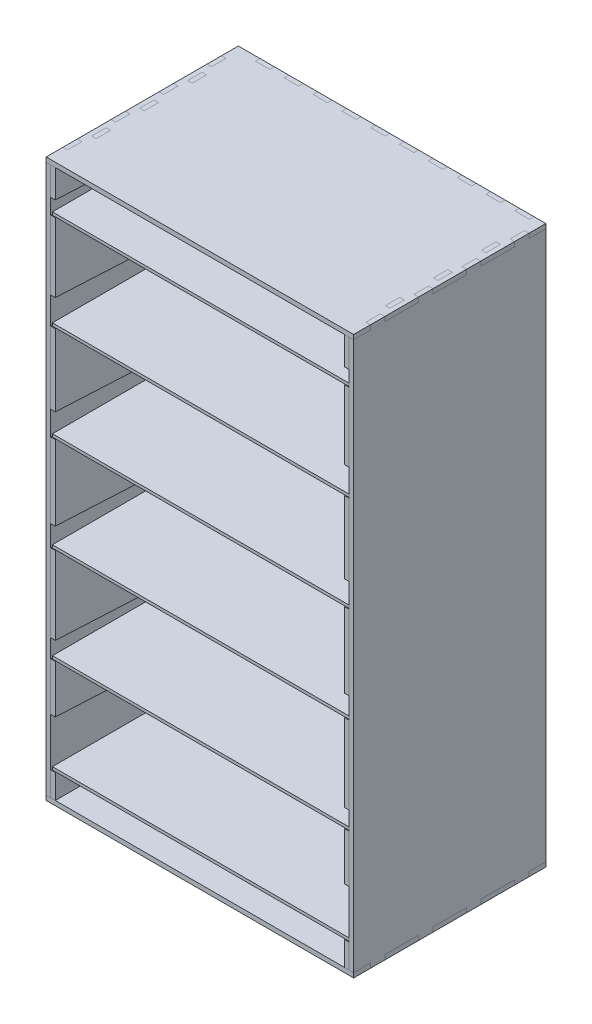
SolidWorks part; units mm, degrees
ref_plane "Front Plane" through (0, 0, 0) normal (0, 0, 1) x (1, 0, 0)
ref_plane "Top Plane" through (0, 0, 0) normal (0, 1, 0) x (1, 0, 0)
ref_plane "Right Plane" through (0, 0, 0) normal (1, 0, 0) x (0, 0, -1)
sketch "Sketch1" plane through (0, 0, 0) normal (0, 0, 1) x (1, 0, 0)
  line L0 (-160, -260) -> (160, -260)
  line L1 (160, -290) -> (-160, -290)
  line L2 (160, -290) -> (160, 290)
  line L3 (160, 290) -> (-160, 290)
  line L4 (-160, -290) -> (-160, 290)
  line L5 (160, -290) -> (-160, 290) construction
  line L6 (160, 290) -> (-160, -290) construction
  line L7 (-160, -160) -> (160, -160)
  line L8 (-160, -60) -> (160, -60)
  line L9 (-160, 40) -> (160, 40)
  line L10 (-160, 140) -> (160, 140)
  line L11 (-160, 240) -> (160, 240)
  point P0 (0, 0)
  dimension "D1" = 320
  dimension "D2" = 580
  dimension "D4" = 30
  dimension "D5" = 100
  dimension "D3" = 6
sketch "Sketch2" plane through (0, 0, 0) normal (0, 0, 1) x (1, 0, 0)
  line L0 (160, -290) -> (160, 290) construction
  line L1 (-160, 290) -> (160, 290)
  line L2 (-160, 290) -> (-160, 285.25)
  line L3 (-160, 285.25) -> (160, 285.25)
  line L4 (160, 290) -> (160, 285.25)
  line L6 (-160, -290) -> (160, -290)
  line L7 (-160, -290) -> (-160, -285.25)
  line L8 (-160, -285.25) -> (160, -285.25)
  line L9 (160, -290) -> (160, -285.25)
  dimension "D1" = 4.75
sketch "Sketch3" plane through (0, 0, 0) normal (0, 1, 0) x (1, 0, 0)
  line L0 (160, 0) -> (-160, 0) construction
  line L1 (-160, 0) -> (160, 0)
  line L2 (-160, 0) -> (-160, -200)
  line L3 (-160, -200) -> (160, -200)
  line L4 (160, 0) -> (160, -200)
  line L5 (160, 0) -> (-160, 0) construction
  line L6 (-155.25, 0) -> (-155.25, -200) construction
  line L7 (-150.5, 0) -> (-150.5, -200) construction
  line L8 (-155.25, -67.5) -> (-160, -67.5)
  line L9 (-155.25, -17.5) -> (-160, -17.5)
  line L10 (-155.25, -17.5) -> (-155.25, -32.5)
  line L11 (-155.25, -32.5) -> (-160, -32.5)
  line L12 (-160, -17.5) -> (-160, -32.5)
  line L13 (-155.25, -17.5) -> (-160, -32.5) construction
  line L14 (-155.25, -32.5) -> (-160, -17.5) construction
  line L15 (-150.5, -57.5) -> (-155.25, -57.5)
  line L16 (-150.5, -57.5) -> (-150.5, -42.5)
  line L17 (-150.5, -42.5) -> (-155.25, -42.5)
  line L18 (-155.25, -57.5) -> (-155.25, -42.5)
  line L19 (-150.5, -57.5) -> (-155.25, -42.5) construction
  line L20 (-150.5, -42.5) -> (-155.25, -57.5) construction
  line L21 (-155.25, -67.5) -> (-155.25, -82.5)
  line L22 (-155.25, -82.5) -> (-160, -82.5)
  line L23 (-160, -67.5) -> (-160, -82.5)
  line L24 (-150.5, -107.5) -> (-155.25, -107.5)
  line L25 (-150.5, -107.5) -> (-150.5, -92.5)
  line L26 (-150.5, -92.5) -> (-155.25, -92.5)
  line L27 (-155.25, -107.5) -> (-155.25, -92.5)
  line L28 (-155.25, -67.5) -> (-160, -82.5) construction
  line L29 (-155.25, -82.5) -> (-160, -67.5) construction
  line L30 (-150.5, -107.5) -> (-155.25, -92.5) construction
  line L31 (-150.5, -92.5) -> (-155.25, -107.5) construction
  line L32 (-155.25, -117.5) -> (-160, -117.5)
  line L33 (-155.25, -117.5) -> (-155.25, -132.5)
  line L34 (-155.25, -132.5) -> (-160, -132.5)
  line L35 (-160, -117.5) -> (-160, -132.5)
  line L36 (-150.5, -157.5) -> (-155.25, -157.5)
  line L37 (-150.5, -157.5) -> (-150.5, -142.5)
  line L38 (-150.5, -142.5) -> (-155.25, -142.5)
  line L39 (-155.25, -157.5) -> (-155.25, -142.5)
  line L40 (-155.25, -117.5) -> (-160, -132.5) construction
  line L41 (-155.25, -132.5) -> (-160, -117.5) construction
  line L42 (-150.5, -157.5) -> (-155.25, -142.5) construction
  line L43 (-150.5, -142.5) -> (-155.25, -157.5) construction
  line L44 (-155.25, -167.5) -> (-160, -167.5)
  line L45 (-155.25, -167.5) -> (-155.25, -182.5)
  line L46 (-155.25, -182.5) -> (-160, -182.5)
  line L47 (-160, -167.5) -> (-160, -182.5)
  line L52 (-155.25, -167.5) -> (-160, -182.5) construction
  line L53 (-155.25, -182.5) -> (-160, -167.5) construction
  line L54 (0, -55) -> (0, 55) construction
  line L55 (155.25, -182.5) -> (160, -167.5) construction
  line L56 (-150.5, -207.5) -> (-155.25, -207.5) [skipped]
  line L57 (-150.5, -207.5) -> (-150.5, -192.5) [skipped]
  line L58 (-150.5, -192.5) -> (-155.25, -192.5) [skipped]
  line L59 (-155.25, -207.5) -> (-155.25, -192.5) [skipped]
  line L60 (-150.5, -207.5) -> (-155.25, -192.5) construction
  line L61 (-150.5, -192.5) -> (-155.25, -207.5) construction
  line L62 (155.25, -167.5) -> (160, -182.5) construction
  line L63 (150.5, -142.5) -> (155.25, -157.5) construction
  line L64 (150.5, -157.5) -> (155.25, -142.5) construction
  line L65 (155.25, -132.5) -> (160, -117.5) construction
  line L66 (155.25, -117.5) -> (160, -132.5) construction
  line L67 (150.5, -92.5) -> (155.25, -107.5) construction
  line L68 (150.5, -107.5) -> (155.25, -92.5) construction
  line L69 (155.25, -82.5) -> (160, -67.5) construction
  line L70 (155.25, -67.5) -> (160, -82.5) construction
  line L71 (150.5, -42.5) -> (155.25, -57.5) construction
  line L72 (150.5, -57.5) -> (155.25, -42.5) construction
  line L73 (155.25, -32.5) -> (160, -17.5) construction
  line L74 (155.25, -17.5) -> (160, -32.5) construction
  line L75 (160, -167.5) -> (160, -182.5)
  line L76 (155.25, -182.5) -> (160, -182.5)
  line L77 (155.25, -167.5) -> (155.25, -182.5)
  line L78 (155.25, -167.5) -> (160, -167.5)
  line L79 (155.25, -157.5) -> (155.25, -142.5)
  line L80 (150.5, -142.5) -> (155.25, -142.5)
  line L81 (150.5, -157.5) -> (150.5, -142.5)
  line L82 (150.5, -157.5) -> (155.25, -157.5)
  line L83 (160, -117.5) -> (160, -132.5)
  line L84 (155.25, -132.5) -> (160, -132.5)
  line L85 (155.25, -117.5) -> (155.25, -132.5)
  line L86 (155.25, -117.5) -> (160, -117.5)
  line L87 (155.25, -107.5) -> (155.25, -92.5)
  line L88 (150.5, -92.5) -> (155.25, -92.5)
  line L89 (150.5, -107.5) -> (150.5, -92.5)
  line L90 (150.5, -107.5) -> (155.25, -107.5)
  line L91 (160, -67.5) -> (160, -82.5)
  line L92 (155.25, -82.5) -> (160, -82.5)
  line L93 (155.25, -67.5) -> (155.25, -82.5)
  line L94 (155.25, -57.5) -> (155.25, -42.5)
  line L95 (150.5, -42.5) -> (155.25, -42.5)
  line L96 (150.5, -57.5) -> (150.5, -42.5)
  line L97 (150.5, -57.5) -> (155.25, -57.5)
  line L98 (160, -17.5) -> (160, -32.5)
  line L99 (155.25, -32.5) -> (160, -32.5)
  line L100 (155.25, -17.5) -> (155.25, -32.5)
  line L101 (155.25, -17.5) -> (160, -17.5)
  line L102 (155.25, -67.5) -> (160, -67.5)
  line L103 (-107.5, 0) -> (-92.5, 0)
  line L104 (-137.5, 0) -> (-122.5, 0)
  line L105 (-137.5, 0) -> (-137.5, -4.75)
  line L106 (-137.5, -4.75) -> (-122.5, -4.75)
  line L107 (-122.5, 0) -> (-122.5, -4.75)
  line L108 (-107.5, 0) -> (-107.5, -4.75)
  line L109 (-107.5, -4.75) -> (-92.5, -4.75)
  line L110 (-92.5, 0) -> (-92.5, -4.75)
  line L111 (-77.5, 0) -> (-62.5, 0)
  line L112 (-77.5, 0) -> (-77.5, -4.75)
  line L113 (-77.5, -4.75) -> (-62.5, -4.75)
  line L114 (-62.5, 0) -> (-62.5, -4.75)
  line L115 (-47.5, 0) -> (-32.5, 0)
  line L116 (-47.5, 0) -> (-47.5, -4.75)
  line L117 (-47.5, -4.75) -> (-32.5, -4.75)
  line L118 (-32.5, 0) -> (-32.5, -4.75)
  line L119 (-17.5, 0) -> (-2.5, 0)
  line L120 (-17.5, 0) -> (-17.5, -4.75)
  line L121 (-17.5, -4.75) -> (-2.5, -4.75)
  line L122 (-2.5, 0) -> (-2.5, -4.75)
  line L123 (12.5, 0) -> (27.5, 0)
  line L124 (12.5, 0) -> (12.5, -4.75)
  line L125 (12.5, -4.75) -> (27.5, -4.75)
  line L126 (27.5, 0) -> (27.5, -4.75)
  line L127 (42.5, 0) -> (57.5, 0)
  line L128 (42.5, 0) -> (42.5, -4.75)
  line L129 (42.5, -4.75) -> (57.5, -4.75)
  line L130 (57.5, 0) -> (57.5, -4.75)
  line L131 (72.5, 0) -> (87.5, 0)
  line L132 (72.5, 0) -> (72.5, -4.75)
  line L133 (72.5, -4.75) -> (87.5, -4.75)
  line L134 (87.5, 0) -> (87.5, -4.75)
  line L135 (102.5, 0) -> (117.5, 0)
  line L136 (102.5, 0) -> (102.5, -4.75)
  line L137 (102.5, -4.75) -> (117.5, -4.75)
  line L138 (117.5, 0) -> (117.5, -4.75)
  line L139 (132.5, 0) -> (147.5, 0)
  line L140 (132.5, 0) -> (132.5, -4.75)
  line L141 (132.5, -4.75) -> (147.5, -4.75)
  line L142 (147.5, 0) -> (147.5, -4.75)
  line L143 (162.5, 0) -> (177.5, 0)
  line L144 (162.5, 0) -> (162.5, -4.75)
  line L145 (162.5, -4.75) -> (177.5, -4.75)
  line L146 (177.5, 0) -> (177.5, -4.75)
  point P10 (-157.625, -25)
  point P19 (-152.875, -200)
  point P21 (-152.875, -50)
  point P26 (-157.625, -75)
  point P31 (-152.875, -100)
  point P36 (-157.625, -125)
  point P41 (-152.875, -150)
  point P46 (-157.625, -175)
  point P92 (157.625, -175)
  point P93 (152.875, -150)
  point P94 (157.625, -125)
  point P95 (152.875, -100)
  point P96 (157.625, -75)
  point P97 (152.875, -50)
  point P98 (157.625, -25)
  dimension "D1" = 200
  dimension "D2" = 4.75
  dimension "D3" = 4.75
  dimension "D4" = 17.5
  dimension "D5" = 15
  dimension "D6" = 10
  dimension "D7" = 15
  dimension "D9" = 10
  dimension "D10" = 17.5
  dimension "D11" = 22.5
  dimension "D12" = 15
  dimension "D14" = 15
  dimension "D15" = 17.5
  dimension "D8" = 4
  dimension "D13" = 11
extrude "Boss-Extrude2" add sketch "Sketch3" against normal blind 4.75 from vertex at 290 contours L93 L102 L4 L99 L100 L101 L1 L2 L9 L10 L11 L8 L21 L22 L32 L33 L34 L44 L45 L46 L3 L76 L77 L78 L84 L85 L86 L92 L97 L96 L95 L94 L90 L89 L88 L87 L82 L81 L80 L79
mirror "Mirror2" about plane through (0, 0, 0) normal (0, 1, 0) of bodies 103
sketch "Sketch4" plane through (0, 0, 0) normal (1, 0, 0) x (0, 0, -1)
  line L1 (0, -290) -> (-200, -290)
  line L2 (0, -290) -> (0, 290)
  line L3 (0, 290) -> (-200, 290)
  line L4 (-200, -290) -> (-200, 290)
  line L5 (0, -290) -> (-200, 290) construction
  line L6 (0, 290) -> (-200, -290) construction
  line L72 (-17.5, -290) -> (0, -290) construction
  line L73 (0, -290) -> (0, -285.25) construction
  line L74 (0, -285.25) -> (-17.5, -285.25) construction
  line L75 (-17.5, -285.25) -> (-17.5, -290) construction
  line L76 (-67.5, -290) -> (-32.5, -290) construction
  line L77 (-32.5, -290) -> (-32.5, -285.25) construction
  line L78 (-32.5, -285.25) -> (-67.5, -285.25) construction
  line L79 (-67.5, -285.25) -> (-67.5, -290) construction
  line L80 (-117.5, -290) -> (-82.5, -290) construction
  line L81 (-82.5, -290) -> (-82.5, -285.25) construction
  line L82 (-82.5, -285.25) -> (-117.5, -285.25) construction
  line L83 (-117.5, -285.25) -> (-117.5, -290) construction
  line L84 (-167.5, -290) -> (-132.5, -290) construction
  line L85 (-132.5, -290) -> (-132.5, -285.25) construction
  line L86 (-132.5, -285.25) -> (-167.5, -285.25) construction
  line L87 (-167.5, -285.25) -> (-167.5, -290) construction
  line L88 (-200, -290) -> (-182.5, -290) construction
  line L89 (-182.5, -290) -> (-182.5, -285.25) construction
  line L90 (-182.5, -285.25) -> (-200, -285.25) construction
  line L91 (-200, -285.25) -> (-200, -290) construction
  line L92 (0, 290) -> (-17.5, 290) construction
  line L93 (-17.5, 290) -> (-17.5, 285.25) construction
  line L94 (-17.5, 285.25) -> (0, 285.25) construction
  line L95 (0, 285.25) -> (0, 290) construction
  line L96 (-32.5, 290) -> (-67.5, 290) construction
  line L97 (-67.5, 290) -> (-67.5, 285.25) construction
  line L98 (-67.5, 285.25) -> (-32.5, 285.25) construction
  line L99 (-32.5, 285.25) -> (-32.5, 290) construction
  line L100 (-82.5, 290) -> (-117.5, 290) construction
  line L101 (-117.5, 290) -> (-117.5, 285.25) construction
  line L102 (-117.5, 285.25) -> (-82.5, 285.25) construction
  line L103 (-82.5, 285.25) -> (-82.5, 290) construction
  line L104 (-132.5, 290) -> (-167.5, 290) construction
  line L105 (-167.5, 290) -> (-167.5, 285.25) construction
  line L106 (-167.5, 285.25) -> (-132.5, 285.25) construction
  line L107 (-132.5, 285.25) -> (-132.5, 290) construction
  line L108 (-182.5, 290) -> (-200, 290) construction
  line L109 (-200, 290) -> (-200, 285.25) construction
  line L110 (-200, 285.25) -> (-182.5, 285.25) construction
  line L111 (-182.5, 285.25) -> (-182.5, 290) construction
  line L112 (-17.5, -290) -> (0, -290)
  line L113 (0, -290) -> (0, -285.25)
  line L114 (0, -285.25) -> (-17.5, -285.25)
  line L115 (-17.5, -285.25) -> (-17.5, -290)
  line L116 (-67.5, -290) -> (-32.5, -290)
  line L117 (-32.5, -290) -> (-32.5, -285.25)
  line L118 (-32.5, -285.25) -> (-67.5, -285.25)
  line L119 (-67.5, -285.25) -> (-67.5, -290)
  line L120 (-117.5, -290) -> (-82.5, -290)
  line L121 (-82.5, -290) -> (-82.5, -285.25)
  line L122 (-82.5, -285.25) -> (-117.5, -285.25)
  line L123 (-117.5, -285.25) -> (-117.5, -290)
  line L124 (-167.5, -290) -> (-132.5, -290)
  line L125 (-132.5, -290) -> (-132.5, -285.25)
  line L126 (-132.5, -285.25) -> (-167.5, -285.25)
  line L127 (-167.5, -285.25) -> (-167.5, -290)
  line L128 (-200, -290) -> (-182.5, -290)
  line L129 (-182.5, -290) -> (-182.5, -285.25)
  line L130 (-182.5, -285.25) -> (-200, -285.25)
  line L131 (-200, -285.25) -> (-200, -290)
  line L132 (0, 290) -> (-17.5, 290)
  line L133 (-17.5, 290) -> (-17.5, 285.25)
  line L134 (-17.5, 285.25) -> (0, 285.25)
  line L135 (0, 285.25) -> (0, 290)
  line L136 (-32.5, 290) -> (-67.5, 290)
  line L137 (-67.5, 290) -> (-67.5, 285.25)
  line L138 (-67.5, 285.25) -> (-32.5, 285.25)
  line L139 (-32.5, 285.25) -> (-32.5, 290)
  line L140 (-82.5, 290) -> (-117.5, 290)
  line L141 (-117.5, 290) -> (-117.5, 285.25)
  line L142 (-117.5, 285.25) -> (-82.5, 285.25)
  line L143 (-82.5, 285.25) -> (-82.5, 290)
  line L144 (-132.5, 290) -> (-167.5, 290)
  line L145 (-167.5, 290) -> (-167.5, 285.25)
  line L146 (-167.5, 285.25) -> (-132.5, 285.25)
  line L147 (-132.5, 285.25) -> (-132.5, 290)
  line L148 (-182.5, 290) -> (-200, 290)
  line L149 (-200, 290) -> (-200, 285.25)
  line L150 (-200, 285.25) -> (-182.5, 285.25)
  line L151 (-182.5, 285.25) -> (-182.5, 290)
extrude "Boss-Extrude3" add sketch "Sketch4" against normal blind 4.75 from vertex at 160 separate body
mirror "Mirror3" about plane through (0, 0, 0) normal (1, 0, 0) of bodies 105
sketch "Sketch5" plane through (0, 0, 0) normal (1, 0, 0) x (0, 0, -1)
  line L0 (-42.5, 290) -> (-57.5, 290) construction
  line L5 (0, -285.25) -> (-200, -285.25)
  line L6 (0, -285.25) -> (0, 285.25)
  line L7 (0, 285.25) -> (-200, 285.25)
  line L8 (-200, -285.25) -> (-200, -260)
  line L9 (0, -285.25) -> (-200, 285.25) construction
  line L10 (0, 285.25) -> (-200, -285.25) construction
  line L11 (-57.5, 290) -> (-57.5, 285.25) construction
  line L12 (-57.5, 285.25) -> (-42.5, 285.25) construction
  line L13 (-42.5, 285.25) -> (-42.5, 290) construction
  line L14 (-92.5, 290) -> (-107.5, 290) construction
  line L15 (-107.5, 290) -> (-107.5, 285.25) construction
  line L16 (-107.5, 285.25) -> (-92.5, 285.25) construction
  line L17 (-92.5, 285.25) -> (-92.5, 290) construction
  line L18 (-142.5, 290) -> (-157.5, 290) construction
  line L19 (-157.5, 290) -> (-157.5, 285.25) construction
  line L20 (-157.5, 285.25) -> (-142.5, 285.25) construction
  line L21 (-142.5, 285.25) -> (-142.5, 290) construction
  line L22 (-57.5, -290) -> (-42.5, -290) construction
  line L23 (-42.5, -290) -> (-42.5, -285.25) construction
  line L24 (-42.5, -285.25) -> (-57.5, -285.25) construction
  line L25 (-57.5, -285.25) -> (-57.5, -290) construction
  line L26 (-107.5, -290) -> (-92.5, -290) construction
  line L27 (-92.5, -290) -> (-92.5, -285.25) construction
  line L28 (-92.5, -285.25) -> (-107.5, -285.25) construction
  line L29 (-107.5, -285.25) -> (-107.5, -290) construction
  line L30 (-157.5, -290) -> (-142.5, -290) construction
  line L31 (-142.5, -290) -> (-142.5, -285.25) construction
  line L32 (-142.5, -285.25) -> (-157.5, -285.25) construction
  line L33 (-157.5, -285.25) -> (-157.5, -290) construction
  line L34 (-42.5, 290) -> (-57.5, 290)
  line L35 (-57.5, 290) -> (-57.5, 285.25)
  line L36 (-57.5, 285.25) -> (-42.5, 285.25)
  line L37 (-42.5, 285.25) -> (-42.5, 290)
  line L38 (-92.5, 290) -> (-107.5, 290)
  line L39 (-107.5, 290) -> (-107.5, 285.25)
  line L40 (-107.5, 285.25) -> (-92.5, 285.25)
  line L41 (-92.5, 285.25) -> (-92.5, 290)
  line L42 (-142.5, 290) -> (-157.5, 290)
  line L43 (-157.5, 290) -> (-157.5, 285.25)
  line L44 (-157.5, 285.25) -> (-142.5, 285.25)
  line L45 (-142.5, 285.25) -> (-142.5, 290)
  line L46 (-57.5, -290) -> (-42.5, -290)
  line L47 (-42.5, -290) -> (-42.5, -285.25)
  line L48 (-42.5, -285.25) -> (-57.5, -285.25)
  line L49 (-57.5, -285.25) -> (-57.5, -290)
  line L50 (-107.5, -290) -> (-92.5, -290)
  line L51 (-92.5, -290) -> (-92.5, -285.25)
  line L52 (-92.5, -285.25) -> (-107.5, -285.25)
  line L53 (-107.5, -285.25) -> (-107.5, -290)
  line L54 (-157.5, -290) -> (-142.5, -290)
  line L55 (-142.5, -290) -> (-142.5, -285.25)
  line L56 (-142.5, -285.25) -> (-157.5, -285.25)
  line L57 (-157.5, -285.25) -> (-157.5, -290)
  line L58 (-200, -151) -> (-30, -151)
  line L61 (-200, -260) -> (-30, -260)
  line L63 (-200, -151) -> (-200, -160)
  line L64 (-200, -160) -> (-30, -160)
  line L65 (-30, -151) -> (-30, -160)
  line L66 (-200, -48) -> (-30, -48)
  line L67 (-200, -48) -> (-200, -60)
  line L68 (-200, -60) -> (-30, -60)
  line L69 (-30, -48) -> (-30, -60)
  line L70 (-200, 55) -> (-30, 55)
  line L71 (-200, 55) -> (-200, 40)
  line L72 (-200, 40) -> (-30, 40)
  line L73 (-30, 55) -> (-30, 40)
  line L74 (-200, 158) -> (-30, 158)
  line L75 (-200, 158) -> (-200, 140)
  line L76 (-200, 140) -> (-30, 140)
  line L77 (-30, 158) -> (-30, 140)
  line L78 (-200, 246) -> (-30, 246)
  line L79 (-200, 246) -> (-200, 240)
  line L80 (-200, 240) -> (-30, 240)
  line L81 (-30, 246) -> (-30, 240)
  line L82 (-200, -220) -> (-200, 285.25)
  line L83 (0, 285.25) -> (-4.75, 285.25)
  line L84 (0, 285.25) -> (0, -285.25)
  line L85 (0, -285.25) -> (-4.75, -285.25)
  line L86 (-4.75, 285.25) -> (-4.75, -285.25)
  line L89 (-30, -220) -> (-200, -220)
  line L91 (-30, -220) -> (-30, -260)
  point P0 (-100, 0)
  dimension "D2" = 6
  dimension "D4" = 4.75
  dimension "D5" = 40
  dimension "D3" = 6
extrude "Boss-Extrude4" add sketch "Sketch5" along normal blind 4.75 from surface at -155.25 separate body
chamfer "Chamfer3" distance 10 distance2 200 6 edges at (-152.875, 246, 200) (-152.875, 158, 200) (-152.875, 55, 200) (-152.875, -48, 200) (-152.875, -151, 200) (-152.875, -220, 200)
mirror "Mirror4" about plane through (0, 0, 0) normal (1, 0, 0) of bodies 107
sketch "Sketch6" plane through (0, 0, 0) normal (0, 0, 1) x (1, 0, 0)
  line L1 (155.25, 285.25) -> (-155.25, 285.25)
  line L2 (155.25, 285.25) -> (155.25, -285.25)
  line L3 (155.25, -285.25) -> (-155.25, -285.25)
  line L4 (-155.25, 285.25) -> (-155.25, -285.25)
  line L8 (147.5, -290) -> (132.5, -290) construction
  line L9 (132.5, -290) -> (132.5, -285.25) construction
  line L10 (132.5, -285.25) -> (147.5, -285.25) construction
  line L11 (147.5, -285.25) -> (147.5, -290) construction
  line L12 (117.5, -290) -> (102.5, -290) construction
  line L13 (102.5, -290) -> (102.5, -285.25) construction
  line L14 (102.5, -285.25) -> (117.5, -285.25) construction
  line L15 (117.5, -285.25) -> (117.5, -290) construction
  line L16 (87.5, -290) -> (72.5, -290) construction
  line L17 (72.5, -290) -> (72.5, -285.25) construction
  line L18 (72.5, -285.25) -> (87.5, -285.25) construction
  line L19 (87.5, -285.25) -> (87.5, -290) construction
  line L20 (57.5, -290) -> (42.5, -290) construction
  line L21 (42.5, -290) -> (42.5, -285.25) construction
  line L22 (42.5, -285.25) -> (57.5, -285.25) construction
  line L23 (57.5, -285.25) -> (57.5, -290) construction
  line L24 (27.5, -290) -> (12.5, -290) construction
  line L25 (12.5, -290) -> (12.5, -285.25) construction
  line L26 (12.5, -285.25) -> (27.5, -285.25) construction
  line L27 (27.5, -285.25) -> (27.5, -290) construction
  line L28 (-2.5, -290) -> (-17.5, -290) construction
  line L29 (-17.5, -290) -> (-17.5, -285.25) construction
  line L30 (-17.5, -285.25) -> (-2.5, -285.25) construction
  line L31 (-2.5, -285.25) -> (-2.5, -290) construction
  line L32 (-32.5, -290) -> (-47.5, -290) construction
  line L33 (-47.5, -290) -> (-47.5, -285.25) construction
  line L34 (-47.5, -285.25) -> (-32.5, -285.25) construction
  line L35 (-32.5, -285.25) -> (-32.5, -290) construction
  line L36 (-62.5, -290) -> (-77.5, -290) construction
  line L37 (-77.5, -290) -> (-77.5, -285.25) construction
  line L38 (-77.5, -285.25) -> (-62.5, -285.25) construction
  line L39 (-62.5, -285.25) -> (-62.5, -290) construction
  line L40 (-92.5, -290) -> (-107.5, -290) construction
  line L41 (-107.5, -290) -> (-107.5, -285.25) construction
  line L42 (-107.5, -285.25) -> (-92.5, -285.25) construction
  line L43 (-92.5, -285.25) -> (-92.5, -290) construction
  line L44 (-122.5, -290) -> (-137.5, -290) construction
  line L45 (-137.5, -290) -> (-137.5, -285.25) construction
  line L46 (-137.5, -285.25) -> (-122.5, -285.25) construction
  line L47 (-122.5, -285.25) -> (-122.5, -290) construction
  line L52 (147.5, -290) -> (132.5, -290)
  line L53 (132.5, -290) -> (132.5, -285.25)
  line L54 (132.5, -285.25) -> (147.5, -285.25)
  line L55 (147.5, -285.25) -> (147.5, -290)
  line L56 (117.5, -290) -> (102.5, -290)
  line L57 (102.5, -290) -> (102.5, -285.25)
  line L58 (102.5, -285.25) -> (117.5, -285.25)
  line L59 (117.5, -285.25) -> (117.5, -290)
  line L60 (87.5, -290) -> (72.5, -290)
  line L61 (72.5, -290) -> (72.5, -285.25)
  line L62 (72.5, -285.25) -> (87.5, -285.25)
  line L63 (87.5, -285.25) -> (87.5, -290)
  line L64 (57.5, -290) -> (42.5, -290)
  line L65 (42.5, -290) -> (42.5, -285.25)
  line L66 (42.5, -285.25) -> (57.5, -285.25)
  line L67 (57.5, -285.25) -> (57.5, -290)
  line L68 (27.5, -290) -> (12.5, -290)
  line L69 (12.5, -290) -> (12.5, -285.25)
  line L70 (12.5, -285.25) -> (27.5, -285.25)
  line L71 (27.5, -285.25) -> (27.5, -290)
  line L72 (-2.5, -290) -> (-17.5, -290)
  line L73 (-17.5, -290) -> (-17.5, -285.25)
  line L74 (-17.5, -285.25) -> (-2.5, -285.25)
  line L75 (-2.5, -285.25) -> (-2.5, -290)
  line L76 (-32.5, -290) -> (-47.5, -290)
  line L77 (-47.5, -290) -> (-47.5, -285.25)
  line L78 (-47.5, -285.25) -> (-32.5, -285.25)
  line L79 (-32.5, -285.25) -> (-32.5, -290)
  line L80 (-62.5, -290) -> (-77.5, -290)
  line L81 (-77.5, -290) -> (-77.5, -285.25)
  line L82 (-77.5, -285.25) -> (-62.5, -285.25)
  line L83 (-62.5, -285.25) -> (-62.5, -290)
  line L84 (-92.5, -290) -> (-107.5, -290)
  line L85 (-107.5, -290) -> (-107.5, -285.25)
  line L86 (-107.5, -285.25) -> (-92.5, -285.25)
  line L87 (-92.5, -285.25) -> (-92.5, -290)
  line L88 (-122.5, -290) -> (-137.5, -290)
  line L89 (-137.5, -290) -> (-137.5, -285.25)
  line L90 (-137.5, -285.25) -> (-122.5, -285.25)
  line L91 (-122.5, -285.25) -> (-122.5, -290)
  line L92 (-137.5, 290) -> (-122.5, 290) construction
  line L93 (-122.5, 290) -> (-122.5, 285.25) construction
  line L94 (-122.5, 285.25) -> (-137.5, 285.25) construction
  line L95 (-137.5, 285.25) -> (-137.5, 290) construction
  line L96 (-107.5, 290) -> (-92.5, 290) construction
  line L97 (-92.5, 290) -> (-92.5, 285.25) construction
  line L98 (-92.5, 285.25) -> (-107.5, 285.25) construction
  line L99 (-107.5, 285.25) -> (-107.5, 290) construction
  line L100 (-47.5, 290) -> (-32.5, 290) construction
  line L101 (-32.5, 290) -> (-32.5, 285.25) construction
  line L102 (-32.5, 285.25) -> (-47.5, 285.25) construction
  line L103 (-47.5, 285.25) -> (-47.5, 290) construction
  line L104 (-17.5, 290) -> (-2.5, 290) construction
  line L105 (-2.5, 290) -> (-2.5, 285.25) construction
  line L106 (-2.5, 285.25) -> (-17.5, 285.25) construction
  line L107 (-17.5, 285.25) -> (-17.5, 290) construction
  line L108 (12.5, 290) -> (27.5, 290) construction
  line L109 (27.5, 290) -> (27.5, 285.25) construction
  line L110 (27.5, 285.25) -> (12.5, 285.25) construction
  line L111 (12.5, 285.25) -> (12.5, 290) construction
  line L112 (42.5, 290) -> (57.5, 290) construction
  line L113 (57.5, 290) -> (57.5, 285.25) construction
  line L114 (57.5, 285.25) -> (42.5, 285.25) construction
  line L115 (42.5, 285.25) -> (42.5, 290) construction
  line L116 (72.5, 290) -> (87.5, 290) construction
  line L117 (87.5, 290) -> (87.5, 285.25) construction
  line L118 (87.5, 285.25) -> (72.5, 285.25) construction
  line L119 (72.5, 285.25) -> (72.5, 290) construction
  line L120 (102.5, 290) -> (117.5, 290) construction
  line L121 (117.5, 290) -> (117.5, 285.25) construction
  line L122 (117.5, 285.25) -> (102.5, 285.25) construction
  line L123 (102.5, 285.25) -> (102.5, 290) construction
  line L124 (132.5, 290) -> (147.5, 290) construction
  line L125 (147.5, 290) -> (147.5, 285.25) construction
  line L126 (147.5, 285.25) -> (132.5, 285.25) construction
  line L127 (132.5, 285.25) -> (132.5, 290) construction
  line L133 (-137.5, 290) -> (-122.5, 290)
  line L134 (-122.5, 290) -> (-122.5, 285.25)
  line L135 (-122.5, 285.25) -> (-137.5, 285.25)
  line L136 (-137.5, 285.25) -> (-137.5, 290)
  line L137 (-107.5, 290) -> (-92.5, 290)
  line L138 (-92.5, 290) -> (-92.5, 285.25)
  line L139 (-92.5, 285.25) -> (-107.5, 285.25)
  line L140 (-107.5, 285.25) -> (-107.5, 290)
  line L141 (-47.5, 290) -> (-32.5, 290)
  line L142 (-32.5, 290) -> (-32.5, 285.25)
  line L143 (-32.5, 285.25) -> (-47.5, 285.25)
  line L144 (-47.5, 285.25) -> (-47.5, 290)
  line L145 (-17.5, 290) -> (-2.5, 290)
  line L146 (-2.5, 290) -> (-2.5, 285.25)
  line L147 (-2.5, 285.25) -> (-17.5, 285.25)
  line L148 (-17.5, 285.25) -> (-17.5, 290)
  line L149 (12.5, 290) -> (27.5, 290)
  line L150 (27.5, 290) -> (27.5, 285.25)
  line L151 (27.5, 285.25) -> (12.5, 285.25)
  line L152 (12.5, 285.25) -> (12.5, 290)
  line L153 (42.5, 290) -> (57.5, 290)
  line L154 (57.5, 290) -> (57.5, 285.25)
  line L155 (57.5, 285.25) -> (42.5, 285.25)
  line L156 (42.5, 285.25) -> (42.5, 290)
  line L157 (72.5, 290) -> (87.5, 290)
  line L158 (87.5, 290) -> (87.5, 285.25)
  line L159 (87.5, 285.25) -> (72.5, 285.25)
  line L160 (72.5, 285.25) -> (72.5, 290)
  line L161 (102.5, 290) -> (117.5, 290)
  line L162 (117.5, 290) -> (117.5, 285.25)
  line L163 (117.5, 285.25) -> (102.5, 285.25)
  line L164 (102.5, 285.25) -> (102.5, 290)
  line L165 (132.5, 290) -> (147.5, 290)
  line L166 (147.5, 290) -> (147.5, 285.25)
  line L167 (147.5, 285.25) -> (132.5, 285.25)
  line L168 (132.5, 285.25) -> (132.5, 290)
  line L177 (-62.5, 290) -> (-77.5, 290)
  line L178 (-62.5, 285.25) -> (-62.5, 290)
  line L179 (-77.5, 285.25) -> (-62.5, 285.25)
  line L180 (-77.5, 290) -> (-77.5, 285.25)
  line L181 (-62.5, 290) -> (-77.5, 290)
  line L182 (-62.5, 285.25) -> (-62.5, 290)
  line L183 (-77.5, 285.25) -> (-62.5, 285.25)
  line L184 (-77.5, 290) -> (-77.5, 285.25)
  dimension "D1" = 0
extrude "Boss-Extrude5" add sketch "Sketch6" along normal blind 4.75 separate body
sketch "Sketch7" plane through (0, 0, 0) normal (0, 1, 0) x (1, 0, 0)
  line L0 (155.25, -200) -> (155.25, -30) construction
  line L1 (-150.5, -4.75) -> (150.5, -4.75) construction
  line L2 (-150.5, -4.75) -> (-150.5, -200) construction
  line L3 (-150.5, -200) -> (150.5, -200) construction
  line L4 (150.5, -4.75) -> (150.5, -200) construction
  line L5 (155.25, -30) -> (150.5, -30) construction
  line L6 (150.5, -30) -> (150.5, -200) construction
  line L7 (150.5, -200) -> (155.25, -200) construction
  line L8 (-155.25, -30) -> (-155.25, -200) construction
  line L10 (-150.5, -200) -> (-150.5, -30) construction
  line L11 (-150.5, -30) -> (-155.25, -30) construction
  line L12 (155.25, -200) -> (155.25, -30) construction
  line L13 (155.25, -30) -> (150.5, -30) construction
  line L14 (150.5, -30) -> (150.5, -200) construction
  line L15 (150.5, -200) -> (155.25, -200) construction
  line L16 (-155.25, -30) -> (-155.25, -200) construction
  line L17 (-155.25, -200) -> (-150.5, -200) construction
  line L18 (-150.5, -200) -> (-150.5, -30) construction
  line L19 (-150.5, -30) -> (-155.25, -30) construction
  line L20 (-149.75, -5.5) -> (-149.75, -199.25)
  line L21 (-149.75, -199.25) -> (149.75, -199.25)
  line L22 (149.75, -5.5) -> (149.75, -199.25)
  line L23 (-149.75, -5.5) -> (149.75, -5.5)
  line L24 (0, -319) -> (0, 319) construction
  line L25 (-149.75, -30) -> (-154.25, -30)
  line L26 (-149.75, -30) -> (-149.75, -199.25)
  line L27 (-149.75, -199.25) -> (-154.25, -199.25)
  line L28 (-154.25, -30) -> (-154.25, -199.25)
  line L29 (149.75, -199.25) -> (154.25, -199.25)
  line L30 (154.25, -30) -> (154.25, -199.25)
  line L31 (149.75, -30) -> (154.25, -30)
  line L32 (149.75, -30) -> (149.75, -199.25)
  dimension "D2" = 1
  dimension "D1" = 0.75
extrude "Boss-Extrude6" add sketch "Sketch7" along normal blind 3 from surface at -260 separate body contours L23 L20 L21 L22 | L25 L28 L27 L20 | L31 L22 L29 L30 starting at face at (-152.875, -260, 115)
pattern_linear "LPattern1" count 6 spacing 100 along (0, 1, 0) of "Boss-Extrude6"
